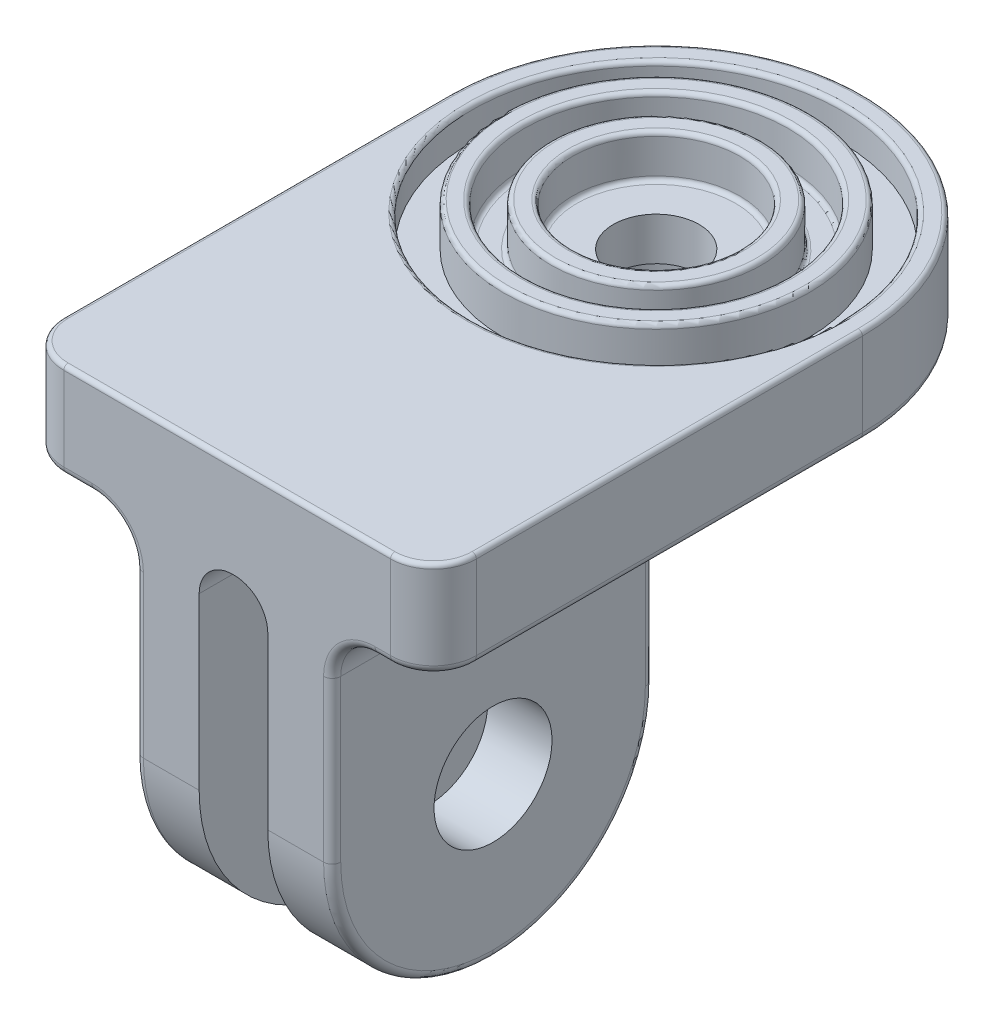
SolidWorks part; units mm, degrees
ref_plane "Ebene vorne" through (0, 0, 0) normal (0, 0, 1) x (1, 0, 0)
ref_plane "Ebene oben" through (0, 0, 0) normal (0, 1, 0) x (1, 0, 0)
ref_plane "Ebene rechts" through (0, 0, 0) normal (1, 0, 0) x (0, 0, -1)
sketch "Skizze1" plane through (0, 0, 0) normal (0, 1, 0) x (1, 0, 0)
  circle A0 centre (0, 0) radius 3.9
  circle A1 centre (0, 0) radius 4.9
  circle A2 centre (0, 0) radius 7.125
  circle A3 centre (0, 0) radius 6.15
  dimension "D1" = 7.8
  dimension "D2" = 9.8
  dimension "D3" = 14.25
  dimension "D4" = 12.3
extrude "Aufsatz-Linear austragen1" add sketch "Skizze1" along normal blind 2 contours A1 A0 | A2 A3 region at (-4.7614, 0, 0) region at (-6.9235, 0, 0)
sketch "Skizze2" plane through (0, 0, 0) normal (0, 1, 0) x (1, 0, 0)
  circle A0 centre (0, 0) radius 8.6168
  circle A1 centre (0, 0) radius 9.6168
  dimension "D1" = 17.2337
  dimension "D2" = 1
extrude "Aufsatz-Linear austragen2" add sketch "Skizze2" along normal blind 1.5 separate body
sketch "Skizze3" plane through (0, 0, 0) normal (0, -1, 0) x (1, 0, 0)
  circle A0 centre (0, 0) radius 9.6168 construction
  circle A1 centre (0, 0) radius 9.6168
  circle A2 centre (0, 0) radius 2
  dimension "D1" = 4
extrude "Aufsatz-Linear austragen3" add sketch "Skizze3" along normal blind 2
fillet "Verrundung1" radius 0.2 1 edges at (0, 0, 3.9)
fillet "Verrundung2" radius 0.2 2 edges at (0, 0, 6.15) (0, 0, 4.9)
fillet "Verrundung3" radius 0.2 5 edges at (0, 2, 4.9) (0, 2, 3.9) (0, 2, 6.15) (0, 2, 7.125) (0, 1.5, 8.6168)
sketch "Skizze4" plane through (0, 0, 0) normal (0, 1, 0) x (1, 0, 0)
  line L0 (-9.6168, 0) -> (-9.6168, -20)
  line L1 (-9.6168, -20) -> (9.6168, -20)
  line L2 (9.6168, -20) -> (9.6168, 0)
  arc A1 (9.6168, 0) -> (-9.6168, 0) centre (0, 0) ccw
  circle A2 centre (0, 0) radius 3
  dimension "D1" = 6
  dimension "D2" = 20
extrude "Aufsatz-Linear austragen4" add sketch "Skizze4" against normal blind 3
sketch "Skizze5" plane through (0, -3, 0) normal (0, -1, 0) x (1, 0, 0)
  line L0 (-9.6168, 20) -> (9.6168, 20) construction
  line L1 (-4.3058, 20) -> (-1.3058, 20)
  line L2 (-4.3058, 20) -> (-4.3058, 5)
  line L3 (-4.3058, 5) -> (-1.3058, 5)
  line L4 (4.8942, 20) -> (4.8942, 5)
  line L5 (0.2942, 0) -> (0.2942, 20) construction
  line L6 (-1.3058, 20) -> (-1.3058, 5)
  line L7 (1.8942, 20) -> (1.8942, 5)
  line L8 (1.8942, 20) -> (4.8942, 20)
  line L9 (1.8942, 5) -> (4.8942, 5)
  dimension "D1" = 9.2
  dimension "D2" = 4.6
  dimension "D3" = 15
  dimension "D4" = 3.2
  dimension "D5" = 1.6
extrude "Aufsatz-Linear austragen5" add sketch "Skizze5" along normal blind 17
fillet "Verrundung4" radius 7.5 4 edges at (3.3942, -20, 20) (-2.8058, -20, 20) (3.3942, -20, 5) (-2.8058, -20, 5)
sketch "Skizze6" plane through (4.8942, 0, 0) normal (1, 0, 0) x (0, 0, -1)
  line L0 (-20, -12.5) -> (-5, -12.5) construction
  line L1 (-12.5, -20) -> (-12.5, -12.5) construction
  circle A0 centre (-12.5, -12.5) radius 2.75
  dimension "D1" = 5.5
extrude "Schnitt-Linear austragen1" cut sketch "Skizze6" against normal through all
fillet "Verrundung5" radius 2 4 edges at (3.3942, -3, 5) (-2.8058, -3, 5) (-4.3058, -3, 12.5) (4.8942, -3, 12.5)
fillet "Verrundung6" radius 1.56 2 edges at (-1.3058, -3, 11.5) (1.8942, -3, 11.5)
fillet "Verrundung7" radius 0.4 17 edges at (-9.6168, -3, 10) (0, -3, -9.6168) (5.48, -3.5858, 4.4142) (4.8942, -8.75, 5) (4.8942, -17.8033, 7.1967) (4.8942, -17.8033, 17.8033) (8.2555, -3, 20) (5.48, -3.5858, 20) (-4.8916, -3.5858, 4.4142) (-4.3058, -8.75, 5) (-7.9613, -3, 20) (-4.8916, -3.5858, 20) (-4.3058, -8.75, 20) (-4.3058, -17.8033, 17.8033) (9.6168, -3, 10) (4.8942, -8.75, 20) (-4.3058, -17.8033, 7.1967)
fillet "Verrundung9" radius 2 4 edges at (-9.4997, -2.8828, 19.8828) (9.4997, -2.8828, 19.8828) (9.6168, -1.3, 20) (-9.6168, -1.3, 20)
sketch "Skizze7" plane through (0, 0, 0) normal (0, 1, 0) x (1, 0, 0)
  line L3 (-7.6168, -20) -> (7.6168, -20)
  line L4 (9.6168, -18) -> (9.6168, 0)
  line L5 (-9.6168, 0) -> (-9.6168, -18)
  line L6 (-7.6168, -20) -> (7.6168, -20)
  line L7 (9.6168, -18) -> (9.6168, 0)
  line L8 (-9.6168, 0) -> (-9.6168, -18)
  arc A3 (7.6168, -20) -> (9.6168, -18) centre (7.6168, -18) ccw
  arc A4 (-9.6168, 0) -> (9.6168, 0) centre (0, 0) ccw
  arc A5 (-9.6168, -18) -> (-7.6168, -20) centre (-7.6168, -18) ccw
  arc A6 (7.6168, -20) -> (9.6168, -18) centre (7.6168, -18) ccw
  arc A7 (-9.6168, 0) -> (9.6168, 0) centre (0, 0) ccw
  arc A8 (-9.6168, -18) -> (-7.6168, -20) centre (-7.6168, -18) ccw
  dimension "D1" = 0
extrude "Aufsatz-Linear austragen6" add sketch "Skizze7" along normal up to surface (1.5 mm away) up to face at (0, 1.5, 8.8168)
fillet "Verrundung12" radius 0.2 6 edges at (9.031, 1.5, 19.4142) (0, 1.5, 20) (-9.031, 1.5, 19.4142) (-9.6168, 1.5, 9) (0, 1.5, -9.6168) (9.6168, 1.5, 9)
equation "\"D2@Skizze5\"=\"D1@Skizze5\"/2"
equation "\"D5@Skizze5\"=\"D4@Skizze5\"/2"
